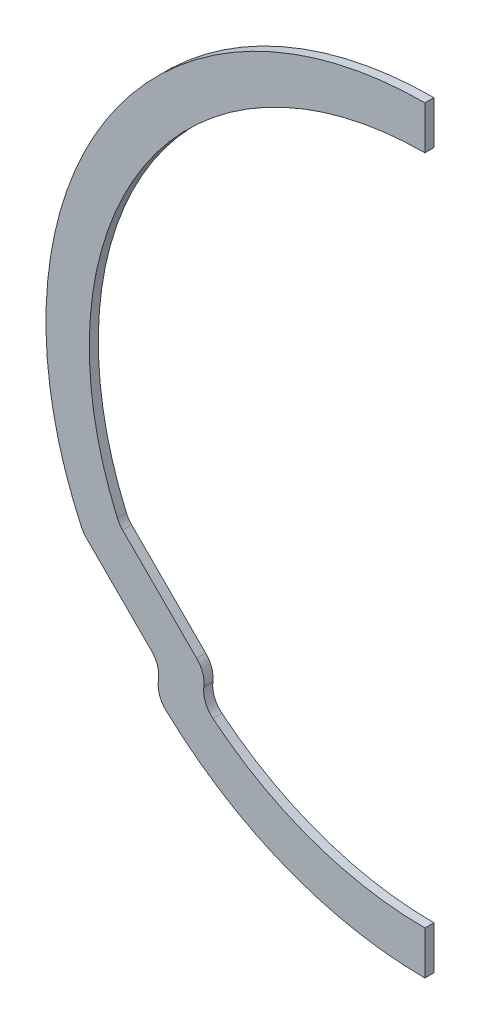
SolidWorks part; units mm, degrees
material "Balsa"
ref_plane "Front Plane" through (0, 0, 0) normal (0, 0, 1) x (1, 0, 0)
ref_plane "Top Plane" through (0, 0, 0) normal (0, 1, 0) x (1, 0, 0)
ref_plane "Right Plane" through (0, 0, 0) normal (1, 0, 0) x (0, 0, -1)
sketch "Sketch1" plane through (0, 0, 0) normal (0, 0, 1) x (1, 0, 0)
  line L0 (0, -110.0909) -> (0, -70.6286) construction
  line L1 (0, 0) -> (0, 245.1538) construction
  line L2 (0, 0) -> (0, 631.6453) construction
  line L3 (-120.188, -34.2725) -> (-93.2472, -61.2132)
  line L4 (0, 0) -> (-284.8905, 0) construction
  line L5 (-93.2472, -61.2132) -> (-94.2927, -70.7977)
  line L8 (-93.2472, -61.2132) -> (-57.7675, -96.693) construction
  arc A0 (-57.7675, -96.693) -> (-120.188, -34.2725) centre (0, 23.495) ccw
  arc A2 (-120.188, -34.2725) -> (-57.7675, -96.693) centre (0, 23.495) ccw construction
  arc A3 (-94.2927, -70.7977) -> (-57.7675, -96.693) centre (0, 23.495) ccw
  point P2 (0, 156.7839)
  point P3 (0, -109.8059)
  point P15 (-93.2472, -61.2132)
  dimension "D1" = 266.5898
  dimension "D2" = 266.7
  dimension "D3" = 23.495
  dimension "D5" = 109.22
  dimension "D6" = 45
  dimension "D7" = 38.1
extrude "Boss-Extrude1" add sketch "Sketch1" along normal mid plane 3.175
sketch "Sketch2" plane through (0, 0, 1.5875) normal (0, 0, 1) x (1, 0, 0)
  line L4 (-77.3048, -55.603) -> (-78.3203, -64.9126)
  line L5 (-107.5191, -25.3887) -> (-77.3048, -55.603)
  line L6 (-77.3048, -55.603) -> (-78.3203, -64.9126)
  line L7 (-107.5191, -25.3887) -> (-77.3048, -55.603)
  arc A2 (-78.3203, -64.9126) -> (-107.5191, -25.3887) centre (0, 23.495) ccw
  arc A3 (-78.3203, -64.9126) -> (-107.5191, -25.3887) centre (0, 23.495) ccw
  dimension "D1" = 15.24
extrude "Cut-Extrude1" cut sketch "Sketch2" against normal up to surface (3.175 mm away) up to face at (-30.5678, -4.3762, -1.5875)
fillet "Fillet1" radius 8.89 6 edges at (-107.5191, -25.3887, 0) (-120.188, -34.2725, 0) (-94.2927, -70.7977, 0) (-93.2472, -61.2132, 0) (-77.3048, -55.603, 0) (-78.3203, -64.9126, 0)
sketch "Sketch3" plane through (0, 0, 0) normal (1, 0, 0) x (0, 0, -1)
  line L1 (-107.0531, 227.715) -> (127.3903, 227.715)
  line L2 (-107.0531, 227.715) -> (-107.0531, -194.8481)
  line L3 (-107.0531, -194.8481) -> (127.3903, -194.8481)
  line L4 (127.3903, 227.715) -> (127.3903, -194.8481)
extrude "Cut-Extrude2" cut sketch "Sketch3" along normal through all
